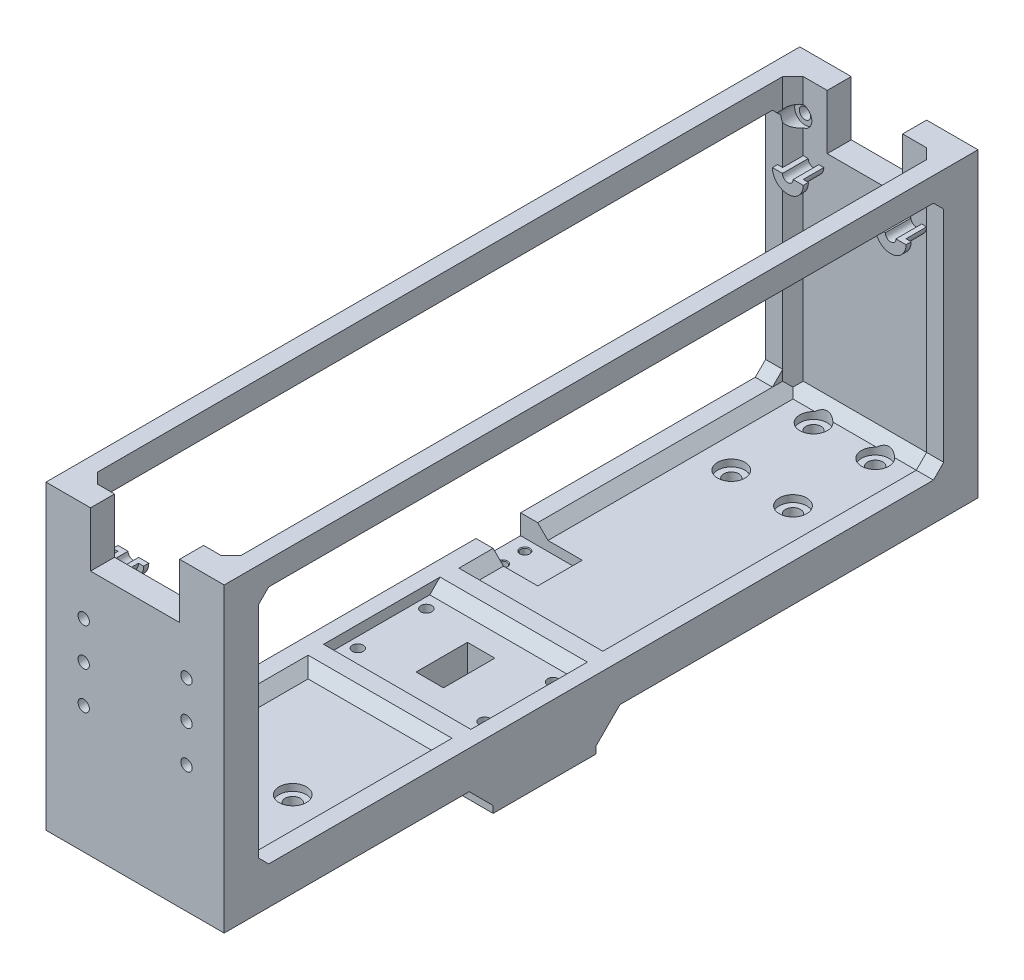
SolidWorks part; units mm, degrees
ref_plane "Front Plane" through (0, 0, 0) normal (0, 0, 1) x (1, 0, 0)
ref_plane "Top Plane" through (0, 0, 0) normal (0, 1, 0) x (1, 0, 0)
ref_plane "Right Plane" through (0, 0, 0) normal (1, 0, 0) x (0, 0, -1)
sketch "Sketch1" plane through (0, 0, 0) normal (0, 1, 0) x (1, 0, 0)
  line L1 (7.7612, 52.9422) -> (59.7612, 52.9422)
  line L2 (7.7612, 52.9422) -> (7.7612, -167.0578)
  line L3 (7.7612, -167.0578) -> (59.7612, -167.0578)
  line L4 (59.7612, 52.9422) -> (59.7612, -167.0578)
  dimension "D1" = 52
  dimension "D2" = 220
extrude "Boss-Extrude1" add sketch "Sketch1" along normal blind 8
sketch "Sketch2" plane through (0, 8, 0) normal (0, 1, 0) x (1, 0, 0)
  line L0 (7.7612, -167.0578) -> (59.7612, -167.0578) construction
  line L1 (7.7612, 52.9422) -> (12.7612, 52.9422)
  line L2 (7.7612, 52.9422) -> (7.7612, -167.0578)
  line L3 (7.7612, -167.0578) -> (12.7612, -167.0578)
  line L4 (12.7612, 52.9422) -> (12.7612, -167.0578)
  dimension "D1" = 5
extrude "Boss-Extrude2" add sketch "Sketch2" along normal blind 80
sketch "Sketch3" plane through (0, 8, 0) normal (0, 1, 0) x (1, 0, 0)
  line L0 (12.7612, -167.0578) -> (12.7612, 52.9422) construction
  line L1 (59.7612, -167.0578) -> (12.7612, -167.0578)
  line L2 (59.7612, -167.0578) -> (59.7612, -160.0578)
  line L3 (59.7612, -160.0578) -> (12.7612, -160.0578)
  line L4 (12.7612, -167.0578) -> (12.7612, -160.0578)
  dimension "D1" = 7
extrude "Boss-Extrude3" add sketch "Sketch3" along normal blind 80
sketch "Sketch4" plane through (0, 8, 0) normal (0, 1, 0) x (1, 0, 0)
  line L0 (12.7612, -160.0578) -> (12.7612, 52.9422) construction
  line L1 (59.7612, 52.9422) -> (12.7612, 52.9422)
  line L2 (59.7612, 52.9422) -> (59.7612, 45.9422)
  line L3 (59.7612, 45.9422) -> (12.7612, 45.9422)
  line L4 (12.7612, 52.9422) -> (12.7612, 45.9422)
  dimension "D1" = 7
extrude "Boss-Extrude4" add sketch "Sketch4" along normal blind 80
sketch "Sketch8" plane through (7.7612, 0, 0) normal (-1, 0, 0) x (0, 0, 1)
  line L0 (-52.9422, 88) -> (167.0578, 88) construction
  line L1 (-42.9422, 88) -> (157.0578, 88)
  line L2 (-42.9422, 88) -> (-42.9422, 8)
  line L3 (-42.9422, 8) -> (157.0578, 8)
  line L4 (157.0578, 88) -> (157.0578, 8)
  line L5 (-52.9422, 88) -> (-52.9422, 0) construction
  line L6 (167.0578, 88) -> (167.0578, 0) construction
  line L7 (-52.9422, 0) -> (167.0578, 0) construction
  dimension "D1" = 0
  dimension "D2" = 10
  dimension "D3" = 10
  dimension "D4" = 8
extrude "Cut-Extrude3" cut sketch "Sketch8" against normal blind 10
sketch "Sketch9" plane through (0, 0, 0) normal (0, -1, 0) x (1, 0, 0)
  circle A0 centre (24.7612, 154.0578) radius 2.2
  circle A1 centre (42.7612, 154.0578) radius 2.2
  circle A2 centre (42.7612, 130.0578) radius 2.2
  circle A3 centre (24.7612, 130.0578) radius 2.2
  dimension "D1" = 4.4
  dimension "D2" = 4.4
  dimension "D3" = 4.4
  dimension "D4" = 4.4
extrude "Cut-Extrude4" cut sketch "Sketch9" against normal blind 8
sketch "Sketch10" plane through (0, 0, 0) normal (0, -1, 0) x (1, 0, 0)
  circle A0 centre (42.7612, -39.9422) radius 2.2
  circle A1 centre (24.7612, -39.9422) radius 2.2
  circle A2 centre (24.7612, -15.9422) radius 2.2
  circle A3 centre (42.7612, -15.9422) radius 2.2
  dimension "D1" = 4.4
  dimension "D2" = 4.4
  dimension "D3" = 4.4
  dimension "D4" = 4.4
extrude "Cut-Extrude5" cut sketch "Sketch10" against normal blind 8
sketch "Sketch12" plane through (0, 8, 0) normal (0, 1, 0) x (1, 0, 0)
  line L0 (12.7612, 45.9422) -> (59.7612, 45.9422) construction
  line L1 (59.7612, -160.0578) -> (54.7612, -160.0578)
  line L2 (59.7612, -160.0578) -> (59.7612, 45.9422)
  line L3 (59.7612, 45.9422) -> (54.7612, 45.9422)
  line L4 (54.7612, -160.0578) -> (54.7612, 45.9422)
  line L6 (7.7612, -157.0578) -> (12.7612, -157.0578)
  line L7 (7.7612, -157.0578) -> (7.7612, 42.9422)
  line L8 (7.7612, 42.9422) -> (12.7612, 42.9422)
  line L9 (12.7612, -157.0578) -> (12.7612, 42.9422)
  dimension "D1" = 5
extrude "Boss-Extrude6" add sketch "Sketch12" along normal blind 3
sketch "Sketch13" plane through (0, 88, 0) normal (0, 1, 0) x (1, 0, 0)
  line L0 (54.7612, 45.9422) -> (54.7612, -160.0578) construction
  line L1 (59.7612, -160.0578) -> (54.7612, -160.0578)
  line L2 (59.7612, -160.0578) -> (59.7612, -157.0578)
  line L3 (59.7612, -157.0578) -> (54.7612, -157.0578)
  line L4 (54.7612, -160.0578) -> (54.7612, -157.0578)
  line L6 (59.7612, 45.9422) -> (54.7612, 45.9422)
  line L7 (59.7612, 45.9422) -> (59.7612, 42.9422)
  line L8 (59.7612, 42.9422) -> (54.7612, 42.9422)
  line L9 (54.7612, 45.9422) -> (54.7612, 42.9422)
  dimension "D1" = 3
  dimension "D2" = 3
extrude "Boss-Extrude7" add sketch "Sketch13" against normal up to surface (77 mm away) up to face at (57.2612, 11, 57.0578)
sketch "Sketch14" plane through (0, 8, 0) normal (0, 1, 0) x (1, 0, 0)
  circle A0 centre (24.7612, 39.9422) radius 4
  circle A1 centre (42.7612, 39.9422) radius 4
  circle A2 centre (42.7612, 15.9422) radius 4
  circle A3 centre (24.7612, 15.9422) radius 4
  circle A4 centre (42.7612, -130.0578) radius 4
  circle A5 centre (24.7612, -130.0578) radius 4
  circle A6 centre (42.7612, -154.0578) radius 4
  circle A7 centre (24.7612, -154.0578) radius 4
  dimension "D1" = 8
  dimension "D2" = 8
  dimension "D3" = 8
  dimension "D4" = 8
  dimension "D5" = 8
  dimension "D6" = 8
  dimension "D7" = 8
  dimension "D8" = 8
extrude "Cut-Extrude7" cut sketch "Sketch14" against normal blind 2
sketch "Sketch15" plane through (0, 0, -45.9422) normal (0, 0, 1) x (1, 0, 0)
  line L0 (12.7612, 88) -> (54.7612, 88) construction
  line L1 (7.7612, 88) -> (7.7612, 0) construction
  circle A0 centre (18.7612, 68) radius 3
  circle A1 centre (48.7612, 68) radius 3
  dimension "D1" = 6
  dimension "D2" = 6
  dimension "D3" = 20
  dimension "D4" = 20
  dimension "D5" = 11
  dimension "D6" = 41
extrude "Boss-Extrude8" add sketch "Sketch15" along normal blind 6
sketch "Sketch16" plane through (0, 0, -39.9422) normal (0, 0, 1) x (1, 0, 0)
  circle A0 centre (18.7612, 68) radius 4.5
  circle A1 centre (48.7612, 68) radius 4.5
  dimension "D1" = 9
  dimension "D2" = 9
extrude "Boss-Extrude9" add sketch "Sketch16" along normal blind 1.5
sketch "Sketch17" plane through (0, 0, -38.4422) normal (0, 0, 1) x (1, 0, 0)
  circle A0 centre (18.7612, 68) radius 1.55
  circle A1 centre (48.7612, 68) radius 1.55
  dimension "D1" = 3.1
  dimension "D2" = 3.1
extrude "Cut-Extrude8" cut sketch "Sketch17" against normal up to surface (7.5 mm away) up to face at (45.7612, 68, -45.9422)
sketch "Sketch19" plane through (0, 0, -42.9422) normal (0, 0, 1) x (1, 0, 0)
  line L0 (12.7612, 88) -> (12.7612, 11) construction
  line L1 (7.7612, 88) -> (12.7612, 88)
  line L2 (7.7612, 88) -> (7.7612, 81)
  line L3 (7.7612, 81) -> (12.7612, 81)
  line L4 (12.7612, 88) -> (12.7612, 81)
  line L5 (59.7612, 11) -> (59.7612, 88) construction
  line L6 (54.7612, 88) -> (59.7612, 88)
  line L7 (54.7612, 88) -> (54.7612, 81)
  line L8 (54.7612, 81) -> (59.7612, 81)
  line L9 (59.7612, 88) -> (59.7612, 81)
  dimension "D1" = 7
  dimension "D2" = 7
extrude "Boss-Extrude11" add sketch "Sketch19" along normal up to surface (200 mm away) up to face at (10.2612, 49.5, 157.0578)
sketch "Sketch20" plane through (0, 0, -45.9422) normal (0, 0, 1) x (1, 0, 0)
  line L0 (54.7612, 88) -> (54.7612, 8) construction
  line L1 (12.7612, 88) -> (54.7612, 88)
  line L2 (12.7612, 88) -> (12.7612, 68)
  line L3 (12.7612, 68) -> (54.7612, 68)
  line L4 (54.7612, 88) -> (54.7612, 68)
  dimension "D1" = 20
extrude "Cut-Extrude9" cut sketch "Sketch20" along normal up to surface (7.5 mm away) up to face at (50.3112, 68, -38.4422)
sketch "Sketch21" plane through (0, 0, 167.0578) normal (0, 0, 1) x (1, 0, 0)
  circle A0 centre (18.7612, 59) radius 1.65
  circle A1 centre (48.7612, 59) radius 1.65
  circle A2 centre (48.7612, 37) radius 1.65
  circle A3 centre (18.7612, 37) radius 1.65
extrude "Cut-Extrude10" cut sketch "Sketch21" against normal blind 10
sketch "Sketch22" plane through (0, 0, 160.0578) normal (0, 0, -1) x (-1, 0, 0)
  circle A0 centre (-18.7612, 59) radius 3
  circle A1 centre (-48.7612, 59) radius 3
  circle A2 centre (-18.7612, 37) radius 3
  circle A3 centre (-48.7612, 37) radius 3
  dimension "D1" = 6
  dimension "D2" = 6
  dimension "D3" = 6
  dimension "D4" = 6
extrude "Cut-Extrude11" cut sketch "Sketch22" against normal blind 2
sketch "Sketch23" plane through (0, 0, 167.0578) normal (0, 0, 1) x (1, 0, 0)
  circle A0 centre (18.7612, 48) radius 1.65
  circle A1 centre (48.7612, 48) radius 1.65
extrude "Cut-Extrude12" cut sketch "Sketch23" against normal blind 10
sketch "Sketch24" plane through (0, 0, 160.0578) normal (0, 0, -1) x (-1, 0, 0)
  circle A0 centre (-48.7612, 48) radius 3
  circle A1 centre (-18.7612, 48) radius 3
  dimension "D1" = 6
  dimension "D2" = 6
extrude "Cut-Extrude13" cut sketch "Sketch24" against normal blind 2
sketch "Sketch25" plane through (0, 88, 0) normal (0, 1, 0) x (1, 0, 0)
  line L0 (7.7612, -167.0578) -> (59.7612, -167.0578) construction
  line L1 (46.7612, -167.0578) -> (20.7612, -167.0578)
  line L2 (46.7612, -167.0578) -> (46.7612, -160.0578)
  line L3 (46.7612, -160.0578) -> (20.7612, -160.0578)
  line L4 (20.7612, -167.0578) -> (20.7612, -160.0578)
  line L5 (54.7612, -160.0578) -> (12.7612, -160.0578) construction
  line L6 (7.7612, 52.9422) -> (7.7612, -167.0578) construction
  line L7 (59.7612, -167.0578) -> (59.7612, 52.9422) construction
  dimension "D1" = 13
  dimension "D2" = 13
extrude "Cut-Extrude14" cut sketch "Sketch25" against normal blind 16
sketch "Sketch26" plane through (0, 88, 0) normal (0, 1, 0) x (1, 0, 0)
  line L0 (59.7612, 52.9422) -> (7.7612, 52.9422) construction
  line L1 (44.7612, 52.9422) -> (22.7612, 52.9422)
  line L2 (44.7612, 52.9422) -> (44.7612, 45.9422)
  line L3 (44.7612, 45.9422) -> (22.7612, 45.9422)
  line L4 (22.7612, 52.9422) -> (22.7612, 45.9422)
  line L5 (12.7612, 45.9422) -> (54.7612, 45.9422) construction
  line L6 (7.7612, 52.9422) -> (7.7612, -167.0578) construction
  line L7 (59.7612, -167.0578) -> (59.7612, 52.9422) construction
  dimension "D1" = 15
  dimension "D2" = 15
extrude "Cut-Extrude15" cut sketch "Sketch26" against normal blind 16
sketch "Sketch30" plane through (0, 88, 0) normal (0, 1, 0) x (1, 0, 0)
  line L0 (12.7612, -160.0578) -> (12.7612, 45.9422) construction
  line L1 (54.7612, -160.0578) -> (12.7612, -160.0578)
  line L2 (54.7612, -160.0578) -> (54.7612, -151.0342)
  line L3 (54.7612, -151.0342) -> (12.7612, -151.0342)
  line L4 (12.7612, -160.0578) -> (12.7612, -151.0342)
sketch "Sketch32" plane through (0, 0, -52.9422) normal (0, 0, -1) x (-1, 0, 0)
  circle A0 centre (-52.2612, 78) radius 1.65
  circle A1 centre (-15.2612, 78) radius 1.65
extrude "Cut-Extrude18" cut sketch "Sketch32" against normal blind 10
sketch "Sketch33" plane through (0, 0, -42.9422) normal (0, 0, 1) x (1, 0, 0)
  circle A0 centre (15.2612, 78) radius 3
  circle A1 centre (52.2612, 78) radius 3
  dimension "D1" = 6
  dimension "D2" = 6
extrude "Cut-Extrude19" cut sketch "Sketch33" against normal blind 4
sketch "Sketch34" plane through (0, 0, 0) normal (0, -1, 0) x (1, 0, 0)
  line L0 (59.7612, 167.0578) -> (59.7612, -52.9422) construction
  line L1 (12.7612, 162.0578) -> (54.7612, 162.0578)
  line L2 (12.7612, 162.0578) -> (12.7612, 122.0578)
  line L3 (12.7612, 122.0578) -> (54.7612, 122.0578)
  line L4 (54.7612, 162.0578) -> (54.7612, 122.0578)
  line L5 (7.7612, -52.9422) -> (7.7612, 167.0578) construction
  line L6 (7.7612, 167.0578) -> (59.7612, 167.0578) construction
  dimension "D1" = 5
  dimension "D2" = 5
  dimension "D3" = 5
  dimension "D4" = 45
extrude "Boss-Extrude14" add sketch "Sketch34" along normal blind 3
sketch "Sketch35" plane through (0, -3, 0) normal (0, -1, 0) x (1, 0, 0)
  line L0 (18.7612, 159.0578) -> (48.7612, 159.0578) construction
  line L1 (18.5612, 159.2578) -> (48.9612, 159.2578)
  line L2 (18.5612, 159.2578) -> (18.5612, 124.8578)
  line L3 (18.5612, 124.8578) -> (48.9612, 124.8578)
  line L4 (48.9612, 159.2578) -> (48.9612, 124.8578)
  line L5 (18.7612, 125.0578) -> (48.7612, 125.0578) construction
  line L6 (48.7612, 133.0578) -> (48.7612, 126.0578) construction
  line L7 (18.7612, 126.0578) -> (18.7612, 133.0578) construction
  dimension "D1" = 0.2
  dimension "D2" = 0.2
  dimension "D3" = 0.2
  dimension "D4" = 0.2
extrude "Cut-Extrude20" cut sketch "Sketch35" against normal blind 3
chamfer "Chamfer1" distance 3 angle 45 4 edges at (33.7612, 0, 162.0578) (54.7612, 0, 142.0578) (33.7612, 0, 122.0578) (12.7612, 0, 142.0578)
sketch "Sketch36" plane through (0, 0, 0) normal (0, -1, 0) x (1, 0, 0)
  line L0 (59.7612, 167.0578) -> (59.7612, -52.9422) construction
  line L1 (12.7612, -7.9422) -> (54.7612, -7.9422)
  line L2 (12.7612, -7.9422) -> (12.7612, -47.9422)
  line L3 (12.7612, -47.9422) -> (54.7612, -47.9422)
  line L4 (54.7612, -7.9422) -> (54.7612, -47.9422)
  line L5 (7.7612, -52.9422) -> (7.7612, 167.0578) construction
  line L6 (59.7612, -52.9422) -> (7.7612, -52.9422) construction
  dimension "D1" = 5
  dimension "D2" = 5
  dimension "D3" = 5
  dimension "D4" = 45
extrude "Boss-Extrude15" add sketch "Sketch36" along normal blind 3
sketch "Sketch37" plane through (0, -3, 0) normal (0, -1, 0) x (1, 0, 0)
  line L0 (18.7612, -10.9422) -> (48.7612, -10.9422) construction
  line L1 (18.6612, -10.8422) -> (48.8612, -10.8422)
  line L2 (18.6612, -10.8422) -> (18.6612, -45.0422)
  line L3 (18.6612, -45.0422) -> (48.8612, -45.0422)
  line L4 (48.8612, -10.8422) -> (48.8612, -45.0422)
  line L5 (48.7612, -11.9422) -> (48.7612, -18.9422) construction
  line L6 (18.7612, -18.9422) -> (18.7612, -11.9422) construction
  line L7 (18.7612, -44.9422) -> (48.7612, -44.9422) construction
  dimension "D1" = 0.1
  dimension "D2" = 0.1
  dimension "D3" = 0.1
  dimension "D4" = 0.1
extrude "Cut-Extrude21" cut sketch "Sketch37" against normal blind 3
chamfer "Chamfer2" distance 3 angle 45 4 edges at (33.7612, 0, -7.9422) (54.7612, 0, -27.9422) (33.7612, 0, -47.9422) (12.7612, 0, -27.9422)
sketch "Sketch38" plane through (7.7612, 0, 0) normal (-1, 0, 0) x (0, 0, 1)
  line L0 (-52.9422, 0) -> (167.0578, 0) construction
  line L1 (58.5578, 0) -> (88.5578, 0)
  line L2 (58.5578, 0) -> (58.5578, -9)
  line L3 (58.5578, -9) -> (88.5578, -9)
  line L4 (88.5578, 0) -> (88.5578, -9)
  line L5 (167.0578, 88) -> (167.0578, 0) construction
  dimension "D1" = 30
  dimension "D2" = 9
  dimension "D3" = 78.5
extrude "Boss-Extrude16" add sketch "Sketch38" against normal up to surface (52 mm away) up to face at (59.7612, 44, 57.0578)
sketch "Sketch39" plane through (0, -9, 0) normal (0, -1, 0) x (1, 0, 0)
  line L0 (59.7612, 58.5578) -> (7.7612, 58.5578) construction
  line L1 (22.7612, 58.5578) -> (44.7612, 58.5578)
  line L2 (22.7612, 58.5578) -> (22.7612, 88.5578)
  line L3 (22.7612, 88.5578) -> (44.7612, 88.5578)
  line L4 (44.7612, 58.5578) -> (44.7612, 88.5578)
  line L5 (59.7612, 88.5578) -> (7.7612, 88.5578) construction
  line L6 (7.7612, 58.5578) -> (7.7612, 88.5578) construction
  line L7 (59.7612, 88.5578) -> (59.7612, 58.5578) construction
  dimension "D1" = 15
  dimension "D2" = 15
extrude "Cut-Extrude22" cut sketch "Sketch39" against normal up to surface (9 mm away) up to face at (33.7612, 0, -27.9422)
chamfer "Chamfer3" distance 7 angle 45 2 edges at (44.7612, 0, 73.5578) (22.7612, 0, 73.5578)
chamfer "Chamfer4" distance 7 angle 45 4 edges at (48.7612, 0, 58.5578) (48.7612, 0, 88.5578) (18.7612, 0, 88.5578) (18.7612, 0, 58.5578)
sketch "Sketch41" plane through (0, -9, 0) normal (0, -1, 0) x (1, 0, 0)
  line L0 (7.7612, 58.5578) -> (7.7612, 88.5578) construction
  line L1 (22.7612, 88.5578) -> (7.7612, 88.5578) construction
  line L2 (22.7612, 58.5578) -> (7.7612, 58.5578) construction
  line L3 (59.7612, 88.5578) -> (44.7612, 88.5578) construction
  line L4 (59.7612, 88.5578) -> (59.7612, 58.5578) construction
  line L5 (59.7612, 58.5578) -> (44.7612, 58.5578) construction
  circle A0 centre (15.2612, 63.5578) radius 1.6
  circle A1 centre (15.2612, 83.5578) radius 1.6
  circle A2 centre (52.2612, 83.5578) radius 1.6
  circle A3 centre (52.2612, 63.5578) radius 1.6
  dimension "D1" = 3.2
  dimension "D2" = 3.2
  dimension "D3" = 3.2
  dimension "D4" = 3.2
  dimension "D5" = 7.5
  dimension "D6" = 7.5
  dimension "D7" = 5
  dimension "D8" = 5
  dimension "D9" = 5
  dimension "D10" = 7.5
  dimension "D11" = 5
  dimension "D12" = 7.5
extrude "Cut-Extrude24" cut sketch "Sketch41" against normal up to surface (20 mm away) up to face at (57.2612, 11, 57.0578)
sketch "Sketch42" plane through (0, 8, 0) normal (0, 1, 0) x (1, 0, 0)
  line L1 (48.2612, -56.5578) -> (55.2612, -56.5578)
  line L2 (48.2612, -56.5578) -> (48.2612, -90.5578)
  line L3 (48.2612, -90.5578) -> (55.2612, -90.5578)
  line L4 (55.2612, -56.5578) -> (55.2612, -90.5578)
  line L5 (19.2612, -56.5578) -> (12.2612, -56.5578)
  line L6 (19.2612, -56.5578) -> (19.2612, -90.5578)
  line L7 (19.2612, -90.5578) -> (12.2612, -90.5578)
  line L8 (12.2612, -56.5578) -> (12.2612, -90.5578)
  circle A0 centre (15.2612, -83.5578) radius 1.6 construction
  circle A1 centre (15.2612, -63.5578) radius 1.6 construction
  circle A2 centre (52.2612, -63.5578) radius 1.6 construction
  circle A3 centre (52.2612, -83.5578) radius 1.6 construction
  dimension "D3" = 4
  dimension "D1" = 3
  dimension "D2" = 7
  dimension "D4" = 7
  dimension "D5" = 4
  dimension "D6" = 3
  dimension "D7" = 7
  dimension "D8" = 7
extrude "Cut-Extrude25" cut sketch "Sketch42" along normal up to surface (3 mm away) up to face at (57.2612, 11, 57.0578)
sketch "Sketch43" plane through (0, 8, 0) normal (0, 1, 0) x (1, 0, 0)
  line L0 (54.7612, -90.5578) -> (54.7612, -160.0578) construction
  line L1 (12.7612, -90.5578) -> (54.7612, -90.5578)
  line L2 (12.7612, -90.5578) -> (12.7612, -95.5578)
  line L3 (12.7612, -95.5578) -> (54.7612, -95.5578)
  line L4 (54.7612, -90.5578) -> (54.7612, -95.5578)
  line L5 (54.7612, 45.9422) -> (54.7612, -56.5578) construction
  line L6 (54.7612, -56.5578) -> (12.7612, -56.5578)
  line L7 (54.7612, -56.5578) -> (54.7612, -51.5578)
  line L8 (54.7612, -51.5578) -> (12.7612, -51.5578)
  line L9 (12.7612, -56.5578) -> (12.7612, -51.5578)
  line L10 (12.7612, -56.5578) -> (12.7612, 45.9422) construction
  dimension "D1" = 5
  dimension "D2" = 5
extrude "Boss-Extrude17" add sketch "Sketch43" along normal blind 3
sketch "Sketch44" plane through (0, 0, 0) normal (0, -1, 0) x (1, 0, 0)
  line L0 (37.7612, 51.5578) -> (37.7612, 95.5578) construction
  line L1 (37.7612, 66.0578) -> (29.7612, 66.0578)
  line L2 (37.7612, 66.0578) -> (37.7612, 81.0578)
  line L3 (37.7612, 81.0578) -> (29.7612, 81.0578)
  line L4 (29.7612, 66.0578) -> (29.7612, 81.0578)
  line L5 (29.7612, 95.5578) -> (29.7612, 51.5578) construction
  line L6 (59.7612, 51.5578) -> (37.7612, 51.5578) construction
  dimension "D1" = 14.5
  dimension "D2" = 15
extrude "Cut-Extrude26" cut sketch "Sketch44" against normal up to surface (8 mm away) up to face at (24.7612, 8, -35.9422)
chamfer "Chamfer5" distance 3 angle 45 2 edges at (33.7612, 8, 51.5578) (33.7612, 8, 95.5578)
chamfer "Chamfer6" distance 3 angle 45 2 edges at (33.7612, 8, 90.5578) (33.7612, 8, 56.5578)
chamfer "Chamfer7" distance 3 angle 45 1 edges at (33.7612, 8, -45.9422)
chamfer "Chamfer8" distance 3 angle 45 5 edges at (33.7612, 8, 160.0578) (57.2612, 11, 157.0578) (10.2612, 11, 157.0578) (57.2612, 11, -42.9422) (10.2612, 11, -42.9422)
chamfer "Chamfer9" distance 3 angle 45 4 edges at (57.2612, 81, -42.9422) (10.2612, 81, -42.9422) (10.2612, 81, 157.0578) (57.2612, 81, 157.0578)
chamfer "Chamfer11" distance 3 angle 45 2 edges at (54.7612, 8, 2.8078) (54.7612, 43.6708, -45.9422)
chamfer "Chamfer13" distance 3 angle 45 2 edges at (54.7612, 83.8292, -45.9422) (12.7612, 83.8292, -45.9422)
sketch "Sketch45" plane through (0, 0, 160.0578) normal (0, 0, -1) x (-1, 0, 0)
  circle A1 centre (-18.7612, 68) radius 3
  circle A2 centre (-48.7612, 68) radius 3
  dimension "D1" = 6
  dimension "D2" = 6
extrude "Boss-Extrude18" add sketch "Sketch45" along normal blind 6
sketch "Sketch46" plane through (0, 0, 154.0578) normal (0, 0, -1) x (-1, 0, 0)
  circle A0 centre (-18.7612, 68) radius 4.5
  circle A1 centre (-48.7612, 68) radius 4.5
  dimension "D1" = 9
  dimension "D2" = 9
extrude "Boss-Extrude19" add sketch "Sketch46" along normal blind 1.5
extrude "Cut-Extrude27" cut sketch "Sketch30" against normal blind 20
chamfer "Chamfer15" distance 3 angle 45 8 edges at (54.7612, 49.5, 160.0578) (12.7612, 49.5, 160.0578) (54.7612, 8, 127.8078) (54.7612, 9.5, 97.0578) (12.7612, 9.5, 97.0578) (12.7612, 8, 127.8078) (12.7612, 9.5, 158.5578) (54.7612, 9.5, 158.5578)
chamfer "Chamfer16" distance 3 angle 45 2 edges at (12.7612, 8, 2.8078) (12.7612, 43.6708, -45.9422)
sketch "Sketch47" plane through (0, 0, 152.5578) normal (0, 0, -1) x (-1, 0, 0)
  line L0 (-44.2612, 68) -> (-53.2612, 68) construction
  line L1 (-14.2612, 68) -> (-23.2612, 68) construction
  circle A0 centre (-48.7612, 68) radius 1.55
  circle A1 centre (-18.7612, 68) radius 1.55
  dimension "D1" = 3.1
  dimension "D2" = 3.1
extrude "Cut-Extrude28" cut sketch "Sketch47" against normal up to surface (7.5 mm away) up to face at (33.0689, 57.5385, 160.0578)
sketch "Sketch48" plane through (0, 11, 0) normal (0, 1, 0) x (1, 0, 0)
  line L0 (7.7612, 39.9422) -> (7.7612, -154.0578) construction
  line L1 (7.7612, -41.5578) -> (25.7612, -41.5578)
  line L2 (7.7612, -41.5578) -> (7.7612, -28.5578)
  line L3 (7.7612, -28.5578) -> (25.7612, -28.5578)
  line L4 (25.7612, -41.5578) -> (25.7612, -28.5578)
  line L5 (54.7612, -51.5578) -> (12.7612, -51.5578) construction
  dimension "D1" = 10
  dimension "D2" = 13
  dimension "D3" = 18
extrude "Cut-Extrude29" cut sketch "Sketch48" against normal blind 5.8
chamfer "Chamfer17" distance 2.8 angle 45 1 edges at (25.7612, 5.2, 35.0578)
sketch "Sketch50" plane through (0, 5.2, 0) normal (0, 1, 0) x (1, 0, 0)
  line L0 (7.7612, -28.5578) -> (7.7612, -41.5578) construction
  line L1 (22.9612, -28.5578) -> (7.7612, -28.5578) construction
  line L2 (7.7612, -41.5578) -> (22.9612, -41.5578) construction
  circle A0 centre (12.2612, -31.8078) radius 1.25
  circle A1 centre (12.2612, -38.3078) radius 1.25
  dimension "D1" = 2.5
  dimension "D2" = 2.5
  dimension "D3" = 4.5
  dimension "D4" = 4.5
  dimension "D5" = 3.25
  dimension "D6" = 3.25
extrude "Cut-Extrude30" cut sketch "Sketch50" against normal up to surface (5.2 mm away) up to face at (33.7612, 0, 29.0578)
chamfer "Chamfer18" distance 0.2 angle 45 2 edges at (12.2612, 5.2, 33.0578) (12.2612, 5.2, 39.5578)
